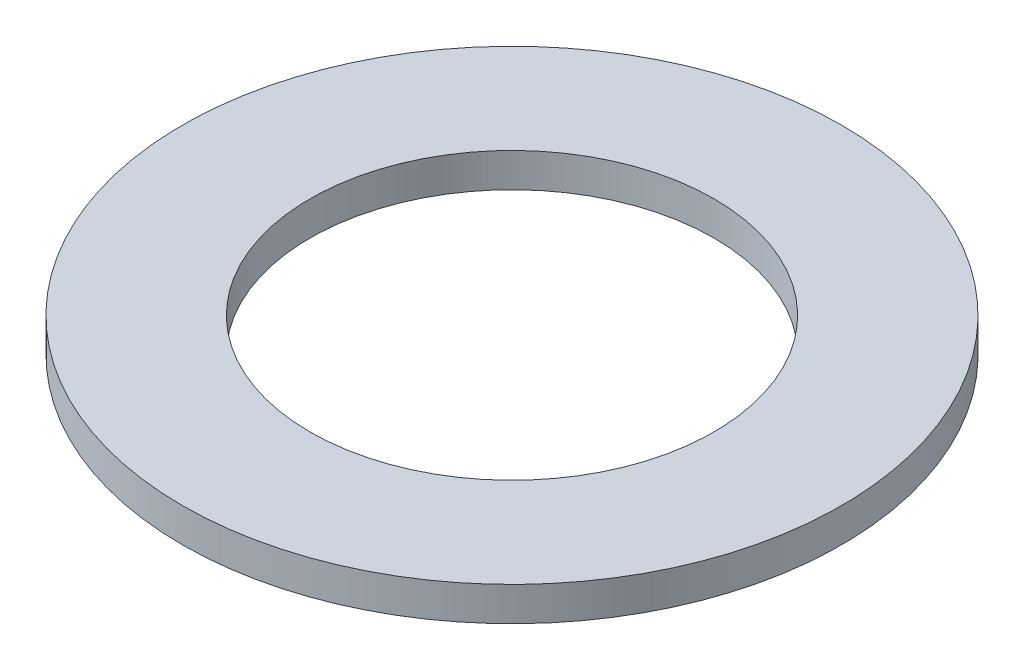
SolidWorks part; units mm, degrees
ref_plane "Front Plane" through (0, 0, 0) normal (0, 0, 1) x (1, 0, 0)
ref_plane "Top Plane" through (0, 0, 0) normal (0, 1, 0) x (1, 0, 0)
ref_plane "Right Plane" through (0, 0, 0) normal (1, 0, 0) x (0, 0, -1)
sketch "Sketch1" plane through (0, 0, 0) normal (0, 1, 0) x (1, 0, 0)
  circle A0 centre (0, 0) radius 77.5
  dimension "FLANGE_OD" = 155
extrude "Boss-Extrude1" add sketch "Sketch1" along normal blind 8
sketch "Sketch2" plane through (0, 0, 0) normal (0, 1, 0) x (1, 0, 0)
  circle A0 centre (0, 0) radius 47.5
  dimension "BORE_D" = 95
extrude "Cut-Extrude1" cut sketch "Sketch2" along normal through all
sketch "Sketch3" plane through (0, 8, 0) normal (0, 1, 0) x (1, 0, 0)
  circle A0 centre (0, 0) radius 29.716 construction
  circle A1 centre (-29.716, 0) radius 3.5483
  dimension "BOLT_D" = 7.0966
  dimension "BOLT_PCD" = 59.432
extrude "Cut-Extrude2" cut sketch "Sketch3" against normal blind 5.1742 rebuild error yes
pattern_circular "CirPattern1" count 6 over 360 rebuild error yes
